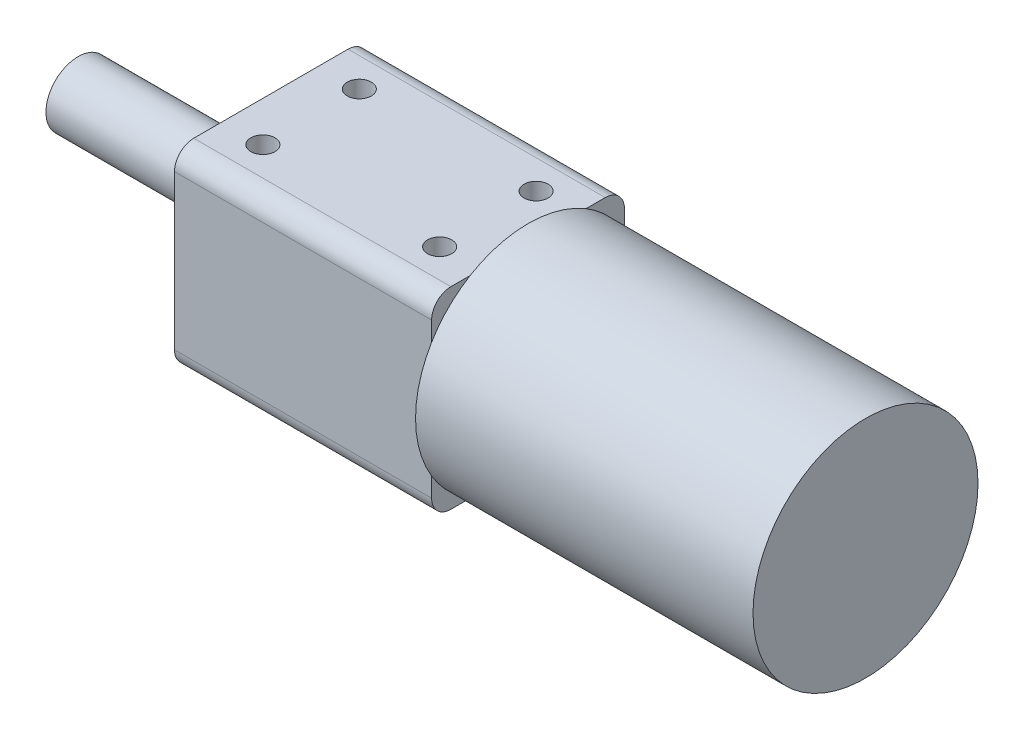
SolidWorks part; units mm, degrees
note: The reader was unsure of these and kept them because the rebuilt part matched: shared geometry of "Sketch1<3>", "Sketch1<4>", "Sketch2<2>".
ref_plane "Front Plane" through (0, 0, 0) normal (0, 0, 1) x (1, 0, 0)
ref_plane "Top Plane" through (0, 0, 0) normal (0, 1, 0) x (1, 0, 0)
ref_plane "Right Plane" through (0, 0, 0) normal (1, 0, 0) x (0, 0, -1)
sketch "Sketch1" plane through (0, 0, 0) normal (1, 0, 0) x (0, 0, -1)
  line L1 (-19.05, -19.05) -> (19.05, -19.05)
  line L2 (-19.05, -19.05) -> (-19.05, 19.05)
  line L3 (-19.05, 19.05) -> (19.05, 19.05)
  line L4 (19.05, -19.05) -> (19.05, 19.05)
  line L5 (-19.05, -19.05) -> (19.05, 19.05) construction
  line L6 (-19.05, 19.05) -> (19.05, -19.05) construction
  circle A0 centre (0, 0) radius 22.225
  circle A1 centre (0, 0) radius 6.35
  dimension "D1" = 38.1
  dimension "D2" = 44.45
  dimension "D3" = 12.7
extrude "Boss-Extrude1" add sketch "Sketch1" along normal blind 66.675 contours A0 | A1 | L3 A0 | L4 A0 | L1 A0 | L2 A0
extrude "Boss-Extrude2" add sketch "Sketch1<3>" against normal blind 50.8 contours A0 L4 L3 | A0 | A0 L3 L2 | A0 L2 L1 | A0 L1 L4 | A1
sketch "Sketch1<3>" plane through (0, 0, 0) normal (1, 0, 0) x (0, 0, -1) same geometry as "Sketch1"
extrude "Boss-Extrude3" add sketch "Sketch1<4>" against normal blind 38.1 from surface at -50.8 contours A1 starting at face at (-50.8, 0, 0)
sketch "Sketch1<4>" plane through (0, 0, 0) normal (1, 0, 0) x (0, 0, -1) same geometry as "Sketch1"
sketch "Sketch2" plane through (0, 19.05, 0) normal (0, 1, 0) x (1, 0, 0)
  line L0 (-50.8, 19.05) -> (0, 19.05) construction
  line L1 (-50.8, -19.05) -> (-50.8, 19.05) construction
  line L2 (-50.8, 0) -> (0, 0) construction
  line L3 (0, -22.225) -> (0, 22.225) construction
  circle A0 centre (-42.8625, 9.525) radius 2.3812
  circle A1 centre (-7.9375, 9.525) radius 2.3813
  circle A2 centre (-7.9375, -9.525) radius 2.3813
  circle A3 centre (-42.8625, -9.525) radius 2.3812
  dimension "D1" = 4.7625
  dimension "D2" = 9.525
  dimension "D3" = 7.9375
  dimension "D5" = 7.9375
  dimension "D4" = 2
extrude "Cut-Extrude1" cut sketch "Sketch2" against normal blind 12.7
extrude "Cut-Extrude2" cut sketch "Sketch2<2>" along normal blind 12.7 from surface at -38.1 starting at face at (-16.9333, -19.05, 0)
sketch "Sketch2<2>" plane through (0, 19.05, 0) normal (0, 1, 0) x (1, 0, 0) same geometry as "Sketch2"
fillet "Fillet1" radius 3.81 4 edges at (-25.4, 19.05, -19.05) (-25.4, -19.05, -19.05) (-25.4, 19.05, 19.05) (-25.4, -19.05, 19.05)
